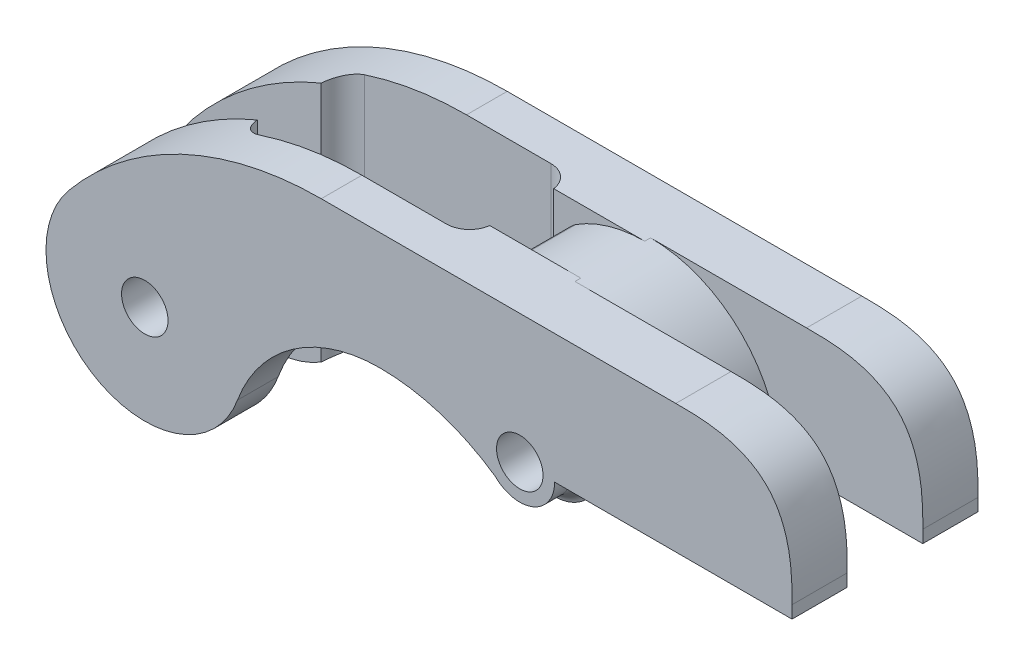
SolidWorks part; units mm, degrees
ref_plane "Płaszczyzna przednia" through (0, 0, 0) normal (0, 0, 1) x (1, 0, 0)
ref_plane "Płaszczyzna górna" through (0, 0, 0) normal (0, 1, 0) x (1, 0, 0)
ref_plane "Płaszczyzna prawa" through (0, 0, 0) normal (1, 0, 0) x (0, 0, -1)
sketch "Szkic1" plane through (0, 0, 0) normal (0, 0, 1) x (1, 0, 0)
  line L0 (4.2089, -3.7911) -> (-3.2157, -11.2157) construction
  line L1 (8.2089, -3.7911) -> (27.6335, -3.7911)
  line L2 (27.6335, 7.2843) -> (-12.8726, 7.2843)
  line L3 (27.6335, -4.9657) -> (27.6335, 4.6918) construction
  line L4 (27.6335, -16.9523) -> (27.6335, -4.9657) construction
  line L5 (27.6335, -3.7911) -> (27.6335, 7.2843)
  line L6 (27.6335, -4.9657) -> (16.1335, -4.9657) construction
  circle A0 centre (-28.0552, -8.3873) radius 2
  arc A1 (-34.6204, -2.9884) -> (-20.0804, -11.3288) centre (-28.0552, -8.3873) ccw
  circle A2 centre (-28.0552, -8.3873) radius 32.5898 construction
  arc A3 (1.3805, -6.6195) -> (7.0373, -0.9627) centre (4.2089, -3.7911) ccw
  arc A4 (-20.0804, -11.3288) -> (1.3805, -6.6195) centre (-7.8428, -15.8428) cw
  arc A5 (-34.6204, -2.9884) -> (7.0373, -0.9627) centre (-12.8726, -20.8726) cw
  circle A6 centre (4.2089, -3.7911) radius 2
  circle A8 centre (-28.0552, -8.3873) radius 6.75 construction
  dimension "D1" = 4
  dimension "D2" = 17
  dimension "D3" = 8
  dimension "D4" = 4
extrude "Dodanie-wyciągnięcie1" add sketch "Szkic1" along normal mid plane 16
sketch "Szkic2" plane through (0, 0, 0) normal (0, 0, 1) x (1, 0, 0)
  line L2 (8.2089, -3.7911) -> (27.6335, -3.7911)
  line L3 (27.6335, 7.2843) -> (-12.8726, 7.2843)
  line L4 (8.2089, -3.7911) -> (27.6335, -3.7911)
  line L5 (27.6335, 7.2843) -> (-12.8726, 7.2843)
  line L7 (27.6335, -3.7911) -> (27.6335, 7.2843)
  line L8 (27.6335, -3.7911) -> (27.6335, 7.2843)
  arc A5 (-12.8726, 7.2843) -> (-34.6204, -2.9884) centre (-12.8726, -20.8726) ccw
  arc A6 (-34.6204, -2.9884) -> (-20.0804, -11.3288) centre (-28.0552, -8.3873) ccw
  arc A7 (1.3805, -6.6195) -> (-20.0804, -11.3288) centre (-7.8428, -15.8428) ccw
  arc A8 (1.3805, -6.6195) -> (8.2089, -3.7911) centre (4.2089, -3.7911) ccw
  arc A10 (-12.8726, 7.2843) -> (-34.6204, -2.9884) centre (-12.8726, -20.8726) ccw
  arc A11 (-34.6204, -2.9884) -> (-20.0804, -11.3288) centre (-28.0552, -8.3873) ccw
  arc A12 (1.3805, -6.6195) -> (-20.0804, -11.3288) centre (-7.8428, -15.8428) ccw
  arc A13 (1.3805, -6.6195) -> (8.2089, -3.7911) centre (4.2089, -3.7911) ccw
  dimension "D1" = 0
extrude "Wytnij-wyciągnięcie1" cut sketch "Szkic2" against normal mid plane 5.5
sketch "Szkic3" plane through (0, 0, -2.75) normal (0, 0, 1) x (1, 0, 0)
  line L0 (8.2089, -3.7911) -> (27.6335, -3.7911) construction
  line L1 (27.6335, 7.2843) -> (-12.8726, 7.2843) construction
  line L2 (15.2843, -3.7911) -> (11.7089, -3.7911)
  line L3 (-1.0944, 1.5122) -> (-3.6226, 4.0404)
  line L4 (4.2089, -3.7911) -> (-6.8665, 7.2843) construction
  arc A0 (11.7089, -3.7911) -> (-1.0944, 1.5122) centre (4.2089, -3.7911) ccw
  arc A2 (15.2843, -3.7911) -> (-3.6226, 4.0404) centre (4.2089, -3.7911) ccw
  dimension "D1" = 7.5
  dimension "D2" = 45
extrude "Dodanie-wyciągnięcie2" add sketch "Szkic3" along normal up to next
sketch "Szkic4" plane through (0, 0, 8) normal (0, 0, 1) x (1, 0, 0)
  line L0 (8.2089, -3.7911) -> (7.2089, -3.7911)
  line L1 (4.2089, -3.7911) -> (-3.2157, -11.2157) construction
  arc A0 (2.0876, -5.9124) -> (7.2089, -3.7911) centre (4.2089, -3.7911) ccw
  arc A1 (2.0876, -5.9124) -> (-7.8428, -2.7991) centre (-7.8428, -20.193) ccw
  arc A2 (1.3805, -6.6195) -> (-20.0804, -11.3288) centre (-7.8428, -15.8428) ccw construction
  arc A4 (1.3805, -6.6195) -> (8.2089, -3.7911) centre (4.2089, -3.7911) ccw construction
  arc A5 (1.3805, -6.6195) -> (8.2089, -3.7911) centre (4.2089, -3.7911) ccw
  arc A6 (1.3805, -6.6195) -> (-7.8428, -2.7991) centre (-7.8428, -15.8428) ccw
  dimension "D1" = 3
extrude "Wytnij-wyciągnięcie2" cut sketch "Szkic4" against normal blind 3
mirror "Lustro1" about plane through (0, 0, 0) normal (0, 0, 1) of "Wytnij-wyciągnięcie2"
sketch "Szkic5" plane through (0, 0, 0) normal (0, 0, 1) x (1, 0, 0)
  line L3 (15.2843, -3.7911) -> (27.6335, -3.7911)
  line L4 (27.6335, -3.7911) -> (27.6335, 7.2843)
  line L5 (27.6335, 7.2843) -> (4.2089, 7.2843)
  line L6 (15.2843, -3.7911) -> (27.6335, -3.7911)
  line L7 (27.6335, -3.7911) -> (27.6335, 7.2843)
  line L8 (27.6335, 7.2843) -> (4.2089, 7.2843)
  arc A2 (15.2843, -3.7911) -> (4.2089, 7.2843) centre (4.2089, -3.7911) ccw
  arc A4 (15.2843, -3.7911) -> (4.2089, 7.2843) centre (4.2089, -3.7911) ccw
  dimension "D1" = 0
extrude "Wytnij-wyciągnięcie3" cut sketch "Szkic5" against normal mid plane 6.5
sketch "Szkic6" plane through (0, 7.2843, 0) normal (0, 1, 0) x (1, 0, 0)
  line L1 (-3.6226, 4.5) -> (-23.6226, 4.5)
  line L2 (-3.6226, 4.5) -> (-3.6226, -4.5)
  line L3 (-3.6226, -4.5) -> (-23.6226, -4.5)
  line L4 (-23.6226, 4.5) -> (-23.6226, -4.5)
  line L5 (-3.6226, 4.5) -> (-23.6226, -4.5) construction
  line L6 (-3.6226, -4.5) -> (-23.6226, 4.5) construction
  line L7 (-3.6226, -2.75) -> (-3.6226, 2.75) construction
  line L8 (-0.3873, 0) -> (-9.3873, 0) construction
  point P0 (-13.6226, 0)
  dimension "D1" = 9
  dimension "D3" = 20
extrude "Wytnij-wyciągnięcie4" cut sketch "Szkic6" against normal up to next
fillet "Zaokrąglenie1" radius 2 5 edges at (-3.6226, 4.0404, 0) (-23.6226, -5.2443, 4.5) (-3.6226, 1.8918, 4.5) (-3.6226, 1.8918, -4.5) (-23.6226, -5.2443, -4.5)
sketch "Szkic8" plane through (0, 0, -8) normal (0, 0, -1) x (-1, 0, 0)
  circle A0 centre (-4.2089, -3.7911) radius 2
  circle A1 centre (-4.2089, -3.7911) radius 1
  circle A2 centre (-4.2089, -3.7911) radius 2 construction
  dimension "D1" = 1
extrude "Dodanie-wyciągnięcie3" add sketch "Szkic8" against normal blind 1
fillet "Zaokrąglenie3" radius 1.5 2 edges at (5.3569, -6.5627, -5) (5.3569, -6.5627, 5)
fillet "Zaokrąglenie4" radius 10 3 edges at (27.6335, 7.2843, 5.625) (7.3804, 7.2843, 8) (15.9212, 7.2843, 3.25)
fillet "Zaokrąglenie5" radius 10 3 edges at (7.3804, 7.2843, -8) (27.6335, 7.2843, -5.625) (15.9212, 7.2843, -3.25)
